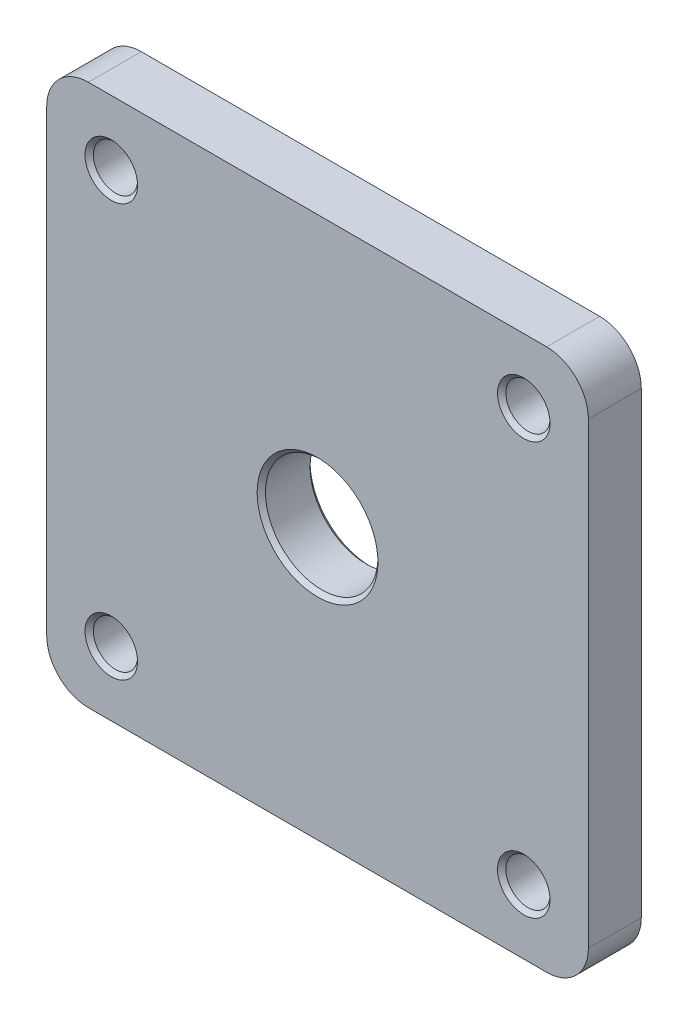
SolidWorks part; units mm, degrees
material "6061 Alloy"
ref_plane "Front Plane" through (0, 0, 0) normal (0, 0, 1) x (1, 0, 0)
ref_plane "Top Plane" through (0, 0, 0) normal (0, 1, 0) x (1, 0, 0)
ref_plane "Right Plane" through (0, 0, 0) normal (1, 0, 0) x (0, 0, -1)
sketch "Sketch1" plane through (0, 0, 0) normal (0, 0, 1) x (1, 0, 0)
  line L1 (-32.5, -32.5) -> (32.5, -32.5)
  line L2 (-32.5, -32.5) -> (-32.5, 32.5)
  line L3 (-32.5, 32.5) -> (32.5, 32.5)
  line L4 (32.5, -32.5) -> (32.5, 32.5)
  line L5 (-32.5, -32.5) -> (32.5, 32.5) construction
  line L6 (-32.5, 32.5) -> (32.5, -32.5) construction
  point P0 (0, 0)
  dimension "D1" = 65
extrude "1/4 in Sheet Metal" add sketch "Sketch1" along normal mid plane 6.35
hole_wizard "M12 Clearance Hole" positions "Sketch3" profile "Sketch4" hole size "M12" standard "ANSI Metric" end condition up to next
sketch "Sketch3" plane through (0, 0, 3.175) normal (0, 0, 1) x (1, 0, 0)
  point P0 (0, 0)
sketch "Sketch4" plane through (0, 0, 3.175) normal (1, 0, 0) x (0, -1, 0)
  line L0 (0, 0) -> (0, 6.35)
  line L1 (0, 6.35) -> (6.75, 6.35)
  line L2 (6.75, 6.35) -> (6.75, 0)
  line L5 (6.75, 0) -> (0, 0)
  line L11 (0, -6.35) -> (0, 107.95) construction
  dimension "Thru Hole Dia." = 13.5
  dimension "Thru Hole Depth" = 6.35
hole_wizard "M5 Clearance Hole1" positions "Sketch5" profile "Sketch6" hole size "M5" standard "ANSI Metric" end condition up to next
sketch "Sketch5" plane through (0, 0, 3.175) normal (0, 0, 1) x (1, 0, 0)
  line L0 (0, 0) -> (35, 0) construction
  line L2 (0, 0) -> (24.7487, 24.7487) construction
  line L4 (0, 0) -> (-24.7487, -24.7487) construction
  line L6 (-24.7487, 24.7487) -> (24.7487, -24.7487) construction
  circle A0 centre (0, 0) radius 35 construction
  point P0 (24.7487, 24.7487)
  point P2 (-24.7487, 24.7487)
  point P4 (-24.7487, -24.7487)
  point P6 (24.7487, -24.7487)
  point P37 (0, 0)
  point P38 (0, 0)
  dimension "D1" = 70
  dimension "D2" = 45
sketch "Sketch6" plane through (24.7487, 24.7487, 3.175) normal (1, 0, 0) x (0, -1, 0)
  line L0 (0, 0) -> (0, 6.35)
  line L1 (0, 6.35) -> (2.65, 6.35)
  line L2 (2.65, 6.35) -> (2.65, 0)
  line L5 (2.65, 0) -> (0, 0)
  line L11 (0, -6.35) -> (0, 107.95) construction
  dimension "Thru Hole Dia." = 5.3
  dimension "Thru Hole Depth" = 6.35
fillet "Fillet1 5 mm" radius 5 4 edges at (-32.5, -32.5, 0) (-32.5, 32.5, 0) (32.5, -32.5, 0) (32.5, 32.5, 0)
chamfer "Chamfer 0.5 mm" distance 0.5 angle 45 10 edges at (-27.3987, -24.7487, -3.175) (-22.0987, -24.7487, 3.175) (22.0987, -24.7487, -3.175) (27.3987, -24.7487, 3.175) (22.0987, 24.7487, -3.175) (27.3987, 24.7487, 3.175) (-27.3987, 24.7487, -3.175) (-22.0987, 24.7487, 3.175) (-6.75, 0, -3.175) (6.75, 0, 3.175)
